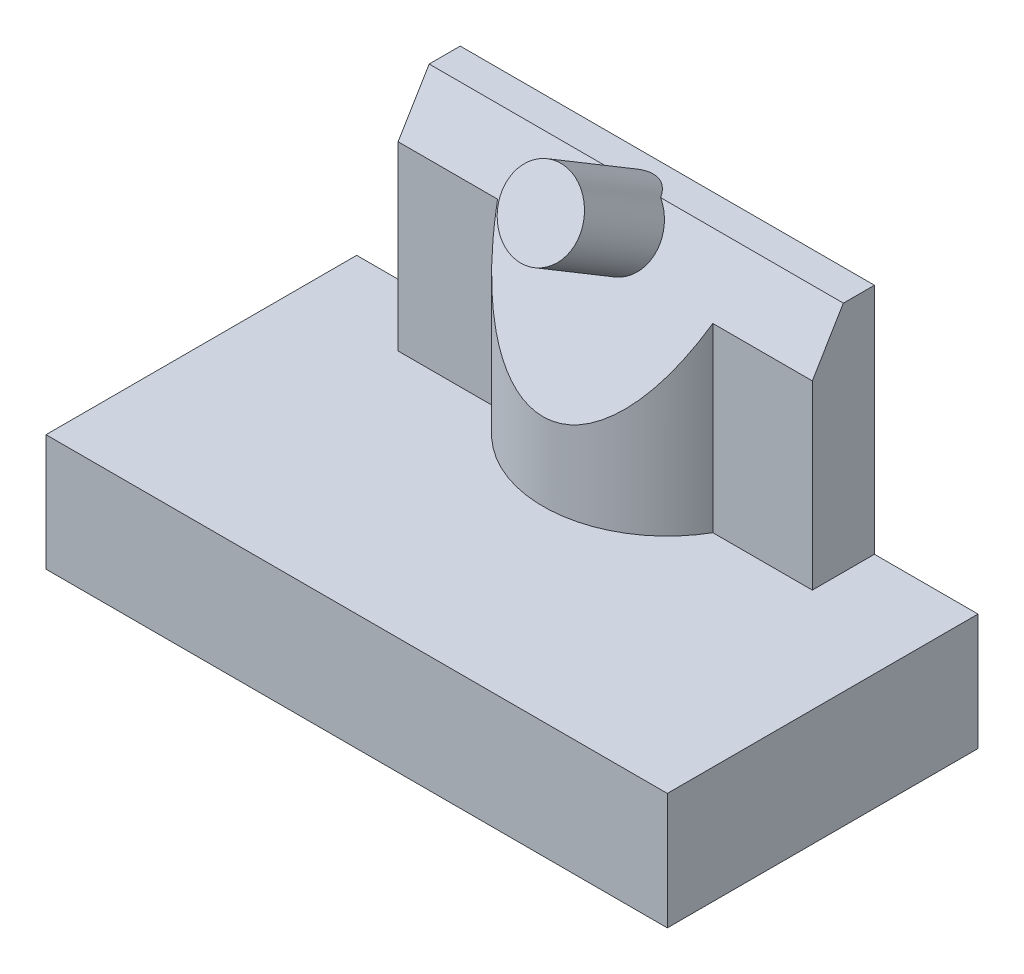
SolidWorks part; units mm, degrees
ref_plane "Front Plane" through (0, 0, 0) normal (0, 0, 1) x (1, 0, 0)
ref_plane "Top Plane" through (0, 0, 0) normal (0, 1, 0) x (1, 0, 0)
ref_plane "Right Plane" through (0, 0, 0) normal (1, 0, 0) x (0, 0, -1)
sketch "Sketch1" plane through (0, 0, 0) normal (0, 1, 0) x (1, 0, 0)
  line L1 (60, -30) -> (-60, -30)
  line L2 (60, -30) -> (60, 30)
  line L3 (60, 30) -> (-60, 30)
  line L4 (-60, -30) -> (-60, 30)
  line L5 (60, -30) -> (-60, 30) construction
  line L6 (60, 30) -> (-60, -30) construction
  point P0 (0, 0)
  dimension "D1" = 120
  dimension "D2" = 60
extrude "Boss-Extrude1" add sketch "Sketch1" along normal blind 22.5
shell "Shell1" thickness 1 removed face at (0, 0, 0)
sketch "Sketch2" plane through (0, 22.5, 0) normal (0, 1, 0) x (1, 0, 0)
  line L0 (0, 30) -> (0, 0) construction
  line L1 (60, 30) -> (-60, 30) construction
  line L2 (-40, 30) -> (40, 30)
  line L3 (40, 30) -> (40, 18)
  line L4 (40, 18) -> (20.7875, 18)
  line L5 (-40, 18) -> (-20.7875, 18)
  line L6 (-40, 30) -> (-40, 18)
  arc A0 (-20.7875, 18) -> (20.7875, 18) centre (0, 30) ccw
  dimension "D1" = 80
  dimension "D3" = 12
extrude "Boss-Extrude2" add sketch "Sketch2" along normal blind 45
sketch "Sketch3" plane through (40, 0, 0) normal (1, 0, 0) x (0, 0, -1)
  line L0 (24, 67.5) -> (5.9975, 67.5)
  line L1 (18, 67.5) -> (30, 67.5) construction
  line L2 (5.9975, 67.5) -> (5.9975, 37.5)
  line L3 (5.9975, 67.5) -> (5.9975, 22.5) construction
  line L4 (5.9975, 37.5) -> (24, 67.5)
  dimension "D1" = 30
extrude "Cut-Extrude1" cut sketch "Sketch3" against normal through all
sketch "Sketch8" plane through (0, 7.2824, 12.1356) normal (0, 0.5145, 0.8575) x (1, 0, 0)
  line L0 (-40, 64.3974) -> (40, 64.3974) construction
  line L1 (-40, 58.5671) -> (-40, 70.2278) construction
  line L2 (40, 58.5671) -> (40, 70.2278) construction
  line L3 (0, 70.2278) -> (0, 35.2408) construction
  line L4 (40, 70.2278) -> (-40, 70.2278) construction
  circle A0 centre (0, 64.3974) radius 7.5
  ellipse E0 centre (0, 81.8885) end of major axis (0, 128.5362) minor radius 24.0025 (-20.7875, 58.5671) -> (20.7875, 58.5671) ccw construction
  dimension "D1" = 15
extrude "Boss-Extrude3" add sketch "Sketch8" against normal up to next and the other way blind 18
